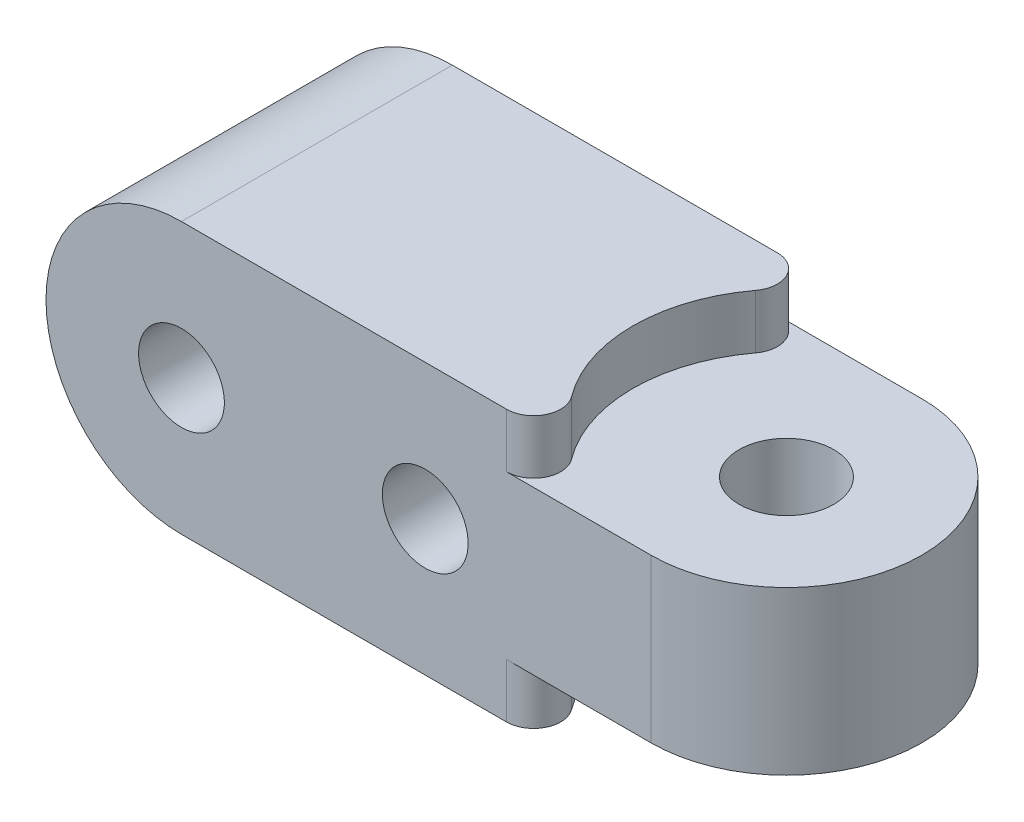
SolidWorks part; units mm, degrees
ref_plane "Front Plane" through (0, 0, 0) normal (0, 0, 1) x (1, 0, 0)
ref_plane "Top Plane" through (0, 0, 0) normal (0, 1, 0) x (1, 0, 0)
ref_plane "Right Plane" through (0, 0, 0) normal (1, 0, 0) x (0, 0, -1)
sketch "Sketch1" plane through (0, 0, 0) normal (0, 1, 0) x (1, 0, 0)
  line L5 (4, 1.5) -> (4, -1.5) construction
  line L6 (-4, -1.5) -> (4, -1.5)
  line L12 (-4, -1.5) -> (-4, 1.5)
  line L13 (-4, 1.5) -> (4, 1.5)
  line L15 (0, 1.5) -> (0, -1.5) construction
  line L16 (4, 0) -> (-4, 0) construction
  line L17 (2.3, 0) -> (2.5, 0) construction
  arc A0 (4, 1.5) -> (4, -1.5) centre (4, 0) cw
  arc A1 (4, 1.5) -> (4, -1.5) centre (4, 0) ccw construction
  arc A2 (2.64, 1.02) -> (2.64, -1.02) centre (4, 0) ccw
  arc A3 (2.64, -1.02) -> (2.4, -1.5) centre (2.4, -1.2) cw
  arc A4 (2.4, 1.5) -> (2.64, 1.02) centre (2.4, 1.2) cw
  arc A5 (3.2, 1.5) -> (2.64, 1.02) centre (4, 0) ccw construction
  arc A6 (2.64, -1.02) -> (3.2, -1.5) centre (4, 0) ccw construction
  circle A7 centre (4, 0) radius 0.525
  point P0 (0, 0)
  dimension "D3" = 0.3
  dimension "D5" = 1.05
  dimension "D1" = 3
  dimension "D2" = 0.2
  dimension "D4" = 8
extrude "Boss-Extrude1" add sketch "Sketch1" along normal mid plane 1.8 contours L13 A4 A2 A3 L6 A0 A7 region at (2.7076, 0, 1.3538)
extrude "Boss-Extrude2" add sketch "Sketch1<4>" along normal mid plane 3 contours A4 L13 L12 L6 A3 A2 region at (-0.7551, 0, 0)
sketch "Sketch1<4>" plane through (0, 0, 0) normal (0, 1, 0) x (1, 0, 0) same geometry as "Sketch1"
hole_wizard "M1.2x0.25 Tapped Hole1" positions "Sketch2" profile "Sketch4" tap size "M1.2x0.25" standard "ANSI Metric" end condition through all
sketch "Sketch2" plane through (0, 0, -1.5) normal (0, 0, -1) x (-1, 0, 0)
  line L0 (-1.5, 0) -> (1.2, 0) construction
  line L6 (-1.5, 0) -> (-2.3, 0) construction
  line L8 (-2.3, 0.9) -> (-2.3, -0.9) construction
  point P0 (-1.5, 0)
  point P3 (1.2, 0)
  dimension "D1" = 2.7
  dimension "D2" = 0.8
sketch "Sketch4" plane through (1.5, 0, -1.5) normal (1, 0, 0) x (0, 1, 0)
  line L0 (0, 0) -> (0, 3)
  line L1 (0, 3) -> (0.475, 3)
  line L2 (0.475, 3) -> (0.475, 0)
  line L5 (0.475, 0) -> (0, 0)
  line L11 (0, -6.35) -> (0, 107.95) construction
  dimension "Thru Tap Drill Dia." = 0.95
  dimension "Thru Tap Drill Depth" = 3
cosmetic thread "Hole Thread1"
cosmetic thread "Hole Thread2"
sketch "Sketch5" plane through (0, 0, -1.5) normal (0, 0, -1) x (-1, 0, 0)
  line L0 (4, 1.5) -> (-2.4, 1.5) construction
  line L1 (4, -1.5) -> (-2.4, -1.5) construction
  line L2 (1.2, -1.5) -> (1.2, 1.5) construction
  line L3 (1.2, 1.5) -> (4, 1.5)
  line L4 (4, 1.5) -> (4, -1.5)
  line L5 (4, -1.5) -> (1.2, -1.5)
  line L6 (4, 1.5) -> (4, -1.5) construction
  arc A0 (1.2, 1.5) -> (1.2, -1.5) centre (1.2, 0) cw
  circle A1 centre (1.2, 0) radius 0.475 construction
extrude "Cut-Extrude1" cut sketch "Sketch5" against normal through all
fillet "Fillet1" [suppressed] radius 0.3
